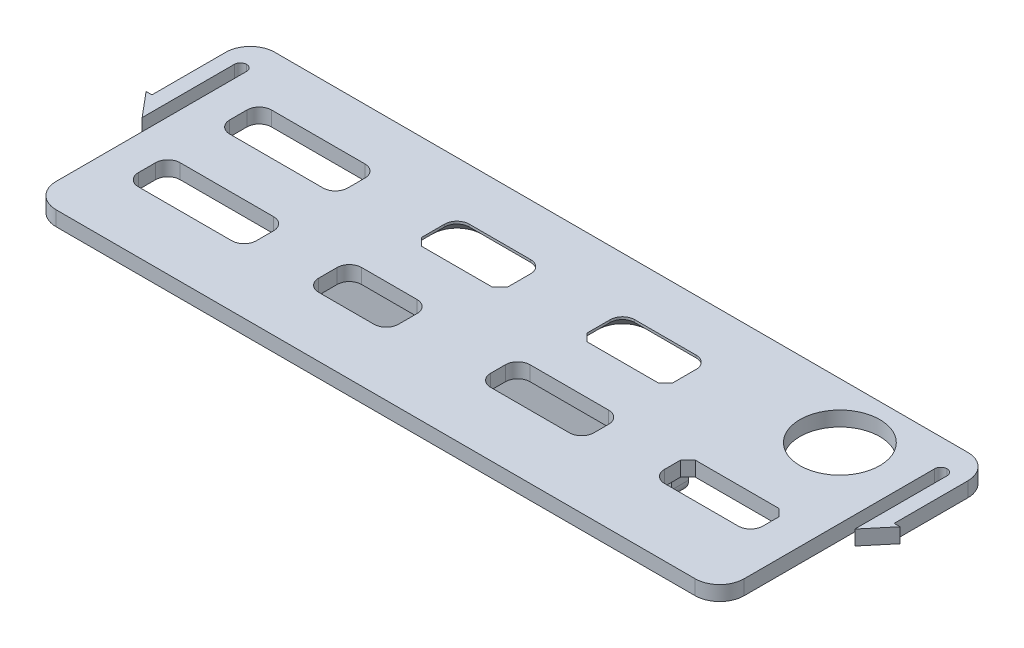
SolidWorks part; units mm, degrees
ref_plane "前视基准面" through (0, 0, 0) normal (0, 0, 1) x (1, 0, 0)
ref_plane "上视基准面" through (0, 0, 0) normal (0, 1, 0) x (1, 0, 0)
ref_plane "右视基准面" through (0, 0, 0) normal (1, 0, 0) x (0, 0, -1)
sketch "草图1" plane through (0, 0, 0) normal (0, 1, 0) x (1, 0, 0)
  line L1 (-30, 10) -> (30, 10)
  line L2 (-30, 10) -> (-30, -10)
  line L3 (-30, -10) -> (30, -10)
  line L4 (30, 10) -> (30, -10)
  line L5 (-30, 10) -> (30, -10) construction
  line L6 (-30, -10) -> (30, 10) construction
  point P0 (0, 0)
  dimension "D1" = 60
  dimension "D2" = 20
extrude "凸台-拉伸1" add sketch "草图1" along normal blind 1.2
sketch "草图4" plane through (0, 1.2, 0) normal (0, 1, 0) x (1, 0, 0)
  line L0 (-30, 10) -> (-30, -10) construction
  line L1 (-25.2717, 5.8) -> (-15.6717, 5.8)
  line L2 (-25.2717, 5.8) -> (-25.2717, 2.4)
  line L3 (-25.2717, 2.4) -> (-15.6717, 2.4)
  line L4 (-15.6717, 5.8) -> (-15.6717, 2.4)
  line L5 (-9.1829, 5.8) -> (-2.1829, 5.8)
  line L6 (-9.1829, 5.8) -> (-9.1829, 2.3)
  line L7 (-9.1829, 2.3) -> (-2.1829, 2.3)
  line L8 (-2.1829, 5.8) -> (-2.1829, 2.3)
  line L9 (4.2885, 5.8) -> (11.2885, 5.8)
  line L10 (4.2885, 5.8) -> (4.2885, 2.3)
  line L11 (4.2885, 2.3) -> (11.2885, 2.3)
  line L12 (11.2885, 5.8) -> (11.2885, 2.3)
  line L13 (17.05, -1.6348) -> (25.05, -1.6348)
  line L14 (17.05, -1.6348) -> (17.05, -4.5348)
  line L15 (17.05, -4.5348) -> (25.05, -4.5348)
  line L16 (25.05, -1.6348) -> (25.05, -4.5348)
  line L17 (3.2, -1.6348) -> (11.6, -1.6348)
  line L18 (3.2, -1.6348) -> (3.2, -4.8348)
  line L19 (3.2, -4.8348) -> (11.6, -4.8348)
  line L20 (11.6, -1.6348) -> (11.6, -4.8348)
  line L21 (-10.5, -1.6348) -> (-4, -1.6348)
  line L22 (-10.5, -1.6348) -> (-10.5, -5.1348)
  line L23 (-10.5, -5.1348) -> (-4, -5.1348)
  line L24 (-4, -1.6348) -> (-4, -5.1348)
  line L25 (-25.2717, -1.6348) -> (-15.6717, -1.6348)
  line L26 (-25.2717, -1.6348) -> (-25.2717, -5.0348)
  line L27 (-25.2717, -5.0348) -> (-15.6717, -5.0348)
  line L28 (-15.6717, -1.6348) -> (-15.6717, -5.0348)
  line L29 (30, 10) -> (-30, 10) construction
  line L30 (-30, -10) -> (30, -10) construction
  line L31 (30, -10) -> (30, 10) construction
  circle A0 centre (22.2985, 5.4832) radius 3.25
  dimension "D21" = 6.5
  dimension "D1" = 3.5
  dimension "D2" = 6.5
  dimension "D3" = 8.4
  dimension "D4" = 3.2
  dimension "D5" = 9.6
  dimension "D6" = 3.4
  dimension "D7" = 7
  dimension "D8" = 8
  dimension "D9" = 2.9
  dimension "D10" = 4.7283
  dimension "D11" = 7.6
  dimension "D12" = 4.9652
  dimension "D13" = 19.5
  dimension "D14" = 33.2
  dimension "D15" = 4.95
  dimension "D16" = 7
  dimension "D17" = 20.8171
  dimension "D18" = 34.2885
  dimension "D19" = 7.7015
  dimension "D20" = 4.5168
  dimension "D22" = 3.5
extrude "切除-拉伸1" cut sketch "草图4" against normal up to next
fillet "圆角2" radius 1 22 edges at (-25.2717, 0.6, -2.4) (-25.2717, 0.6, -5.8) (-15.6717, 0.6, -2.4) (-15.6717, 0.6, -5.8) (-2.1829, 0.6, -5.8) (-9.1829, 0.6, -5.8) (4.2885, 0.6, -5.8) (11.2885, 0.6, -5.8) (25.05, 0.6, 4.5348) (17.05, 0.6, 4.5348) (11.6, 0.6, 4.8348) (11.6, 0.6, 1.6348) (3.2, 0.6, 1.6348) (3.2, 0.6, 4.8348) (-4, 0.6, 5.1348) (-4, 0.6, 1.6348) (-10.5, 0.6, 1.6348) (-10.5, 0.6, 5.1348) (-15.6717, 0.6, 5.0348) (-15.6717, 0.6, 1.6348) (-25.2717, 0.6, 1.6348) (-25.2717, 0.6, 5.0348)
chamfer "倒角1" distance 0.6 angle 45 6 edges at (-9.1829, 0.6, -2.3) (-2.1829, 0.6, -2.3) (4.2885, 0.6, -2.3) (11.2885, 0.6, -2.3) (17.05, 0.6, 1.6348) (25.05, 0.6, 1.6348)
sketch "草图5" plane through (0, 0, 0) normal (0, -1, 0) x (1, 0, 0)
  line L0 (-30, -10) -> (-30, 10) construction
  line L1 (-13.9089, -4.8832) -> (-12.4089, -4.8832)
  line L2 (-13.9089, -4.8832) -> (-13.9089, 3.1168)
  line L3 (-13.9089, 3.1168) -> (-12.4089, 3.1168)
  line L4 (-12.4089, -4.8832) -> (-12.4089, 3.1168)
  line L5 (13.0911, -4.8832) -> (14.5911, -4.8832)
  line L6 (13.0911, -4.8832) -> (13.0911, 3.1168)
  line L7 (13.0911, 3.1168) -> (14.5911, 3.1168)
  line L8 (14.5911, -4.8832) -> (14.5911, 3.1168)
  line L9 (30, -10) -> (-30, -10) construction
  line L10 (30, 10) -> (30, -10) construction
  dimension "D1" = 1.5
  dimension "D2" = 8
  dimension "D3" = 1.5
  dimension "D4" = 8
  dimension "D5" = 16.0911
  dimension "D6" = 5.1168
  dimension "D7" = 5.1168
  dimension "D8" = 15.4089
extrude "凸台-拉伸2" add sketch "草图5" along normal blind 1.2
sketch "草图6" plane through (0, 0, 0) normal (0, -1, 0) x (1, 0, 0)
  line L0 (-13.9089, 3.1168) -> (-13.9089, -4.8832) construction
  line L1 (-13.9089, 0.5168) -> (14.5911, 0.5168)
  line L2 (-13.9089, 0.5168) -> (-13.9089, -0.8832)
  line L3 (-13.9089, -0.8832) -> (14.5911, -0.8832)
  line L4 (14.5911, 0.5168) -> (14.5911, -0.8832)
extrude "凸台-拉伸3" add sketch "草图6" along normal blind 4
fillet "圆角3" radius 1 2 edges at (14.5911, -4, -0.1832) (-13.9089, -4, -0.1832)
chamfer "倒角2" distance 1 angle 45 4 edges at (13.8411, -1.2, -4.8832) (-13.1589, -1.2, -4.8832) (13.8411, -1.2, 3.1168) (-13.1589, -1.2, 3.1168)
chamfer "倒角4" distance 1 angle 45 16 edges at (11.2885, 0, -3.85) (10.9956, 0, -5.5071) (7.7885, 0, -5.8) (4.5814, 0, -5.5071) (10.9885, 0, -2.6) (4.2885, 0, -3.85) (4.5885, 0, -2.6) (7.7885, 0, -2.3) (-9.1829, 0, -3.85) (-2.1829, 0, -3.85) (-8.89, 0, -5.5071) (-2.4758, 0, -5.5071) (-5.6829, 0, -5.8) (-2.4829, 0, -2.6) (-8.8829, 0, -2.6) (-5.6829, 0, -2.3)
sketch "草图7" plane through (0, 1.2, 0) normal (0, 1, 0) x (1, 0, 0)
  line L0 (30, -10) -> (30, 10) construction
  line L1 (30, 10) -> (28, 10)
  line L2 (30, 10) -> (30, -10)
  line L3 (30, -10) -> (28, -10)
  line L4 (28, 10) -> (28, -10)
  line L5 (-30, -10) -> (30, -10) construction
  line L6 (30, 10) -> (-30, 10) construction
  line L7 (-30, 10) -> (-28, 10)
  line L8 (-30, 10) -> (-30, -10)
  line L9 (-30, -10) -> (-28, -10)
  line L10 (-28, 10) -> (-28, -10)
  line L11 (-30, 10) -> (-30, -10) construction
  dimension "D1" = 2
  dimension "D2" = 2
extrude "切除-拉伸2" cut sketch "草图7" against normal blind 5
sketch "草图11" plane through (0, 1.2, 0) normal (0, 1, 0) x (1, 0, 0)
  line L0 (28, 10) -> (30.2, 10)
  line L1 (28, 10) -> (-28, 10) construction
  line L2 (28, 10) -> (28, -10) construction
  line L3 (30.2, 10) -> (30.2, 2)
  line L4 (30.2, 2) -> (31, 2)
  line L5 (31, 2) -> (31, 0)
  line L6 (31, 0) -> (29, 0)
  line L7 (29, 0) -> (29, 8)
  line L8 (29, 8) -> (28, 8)
  line L9 (28, 10) -> (28, -10) construction
  line L10 (28, 8) -> (28, 10)
  line L11 (-28, 10) -> (-30.2, 10)
  line L12 (-30.2, 10) -> (-30.2, 2)
  line L13 (-30.2, 2) -> (-31, 2)
  line L14 (-31, 2) -> (-31, 0)
  line L15 (-31, 0) -> (-29, 0)
  line L16 (-29, 0) -> (-29, 8)
  line L17 (-29, 8) -> (-28, 8)
  line L18 (-28, -10) -> (-28, 10) construction
  line L19 (-28, 8) -> (-28, 10)
  dimension "D1" = 2
  dimension "D2" = 2
  dimension "D3" = 8
  dimension "D4" = 2.2
  dimension "D5" = 2
  dimension "D6" = 0.8
  dimension "D7" = 2.2
  dimension "D8" = 2
  dimension "D9" = 0.8
  dimension "D10" = 8
  dimension "D11" = 2
  dimension "D12" = 2
extrude "凸台-拉伸5" add sketch "草图11" against normal up to surface (1.2 mm away) up to face at (7.7885, 0, -3.95)
fillet "圆角5" radius 2 4 edges at (30.2, 0.6, -10) (-30.2, 0.6, -10) (28, 0.6, 10) (-28, 0.6, 10)
fillet "圆角6" radius 0.5 4 edges at (28, 0.6, -8) (29, 0.6, -8) (-28, 0.6, -8) (-29, 0.6, -8)
chamfer "倒角5" distance 2 angle 50 1 edges at (31, 0.6, 0) first distance on face at (30, 0.6, 0)
chamfer "倒角6" distance 2 angle 50 1 edges at (-31, 0.6, 0) first distance on face at (-30, 0.6, 0)
